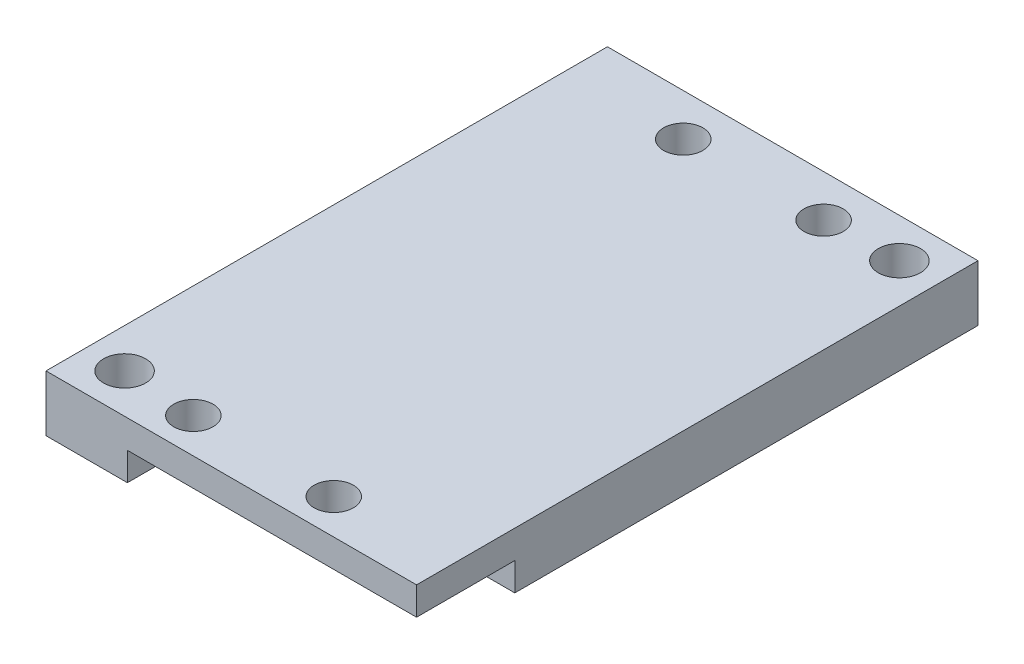
SolidWorks part; units mm, degrees
ref_plane "前视基准面" through (0, 0, 0) normal (0, 0, 1) x (1, 0, 0)
ref_plane "上视基准面" through (0, 0, 0) normal (0, 1, 0) x (1, 0, 0)
ref_plane "右视基准面" through (0, 0, 0) normal (1, 0, 0) x (0, 0, -1)
other "Configuration Table"
sketch "草图1" plane through (0, 0, 0) normal (0, 1, 0) x (1, 0, 0)
  line L1 (-6.6, 10) -> (6.6, 10)
  line L2 (-6.6, 10) -> (-6.6, -10)
  line L3 (-6.6, -10) -> (6.6, -10)
  line L4 (6.6, 10) -> (6.6, -10)
  line L5 (-6.6, 10) -> (6.6, -10) construction
  line L6 (-6.6, -10) -> (6.6, 10) construction
  circle A0 centre (-5.2, -8.6) radius 0.75
  circle A1 centre (5.2, 8.6) radius 0.75
  point P0 (0, 0)
  point P5 (3, -8.5)
  dimension "D7" = 1.5
  dimension "D1" = 20
  dimension "D2" = 13.2
  dimension "D3" = 1.4
  dimension "D4" = 1.4
  dimension "D5" = 1.4
  dimension "D6" = 1.4
extrude "凸台-拉伸1" add sketch "草图1" along normal blind 2 contours L2 L3 L4 L1
extrude "切除-拉伸2" cut sketch "草图1<3>" along normal through all contours A0 | A1
sketch "草图1<3>" plane through (0, 0, 0) normal (0, 1, 0) x (1, 0, 0) same geometry as "草图1"
sketch "草图2" plane through (0, 2, 0) normal (0, 1, 0) x (1, 0, 0)
  line L0 (6.6, 10) -> (6.6, -10) construction
  line L1 (-6.6, 10) -> (3.7, 10)
  line L2 (-6.6, 10) -> (-6.6, 6.5)
  line L3 (-6.6, 6.5) -> (3.7, 6.5)
  line L4 (3.7, 10) -> (3.7, 6.5)
  line L5 (6.6, -10) -> (-3.7, -10)
  line L6 (6.6, -10) -> (6.6, -6.5)
  line L7 (6.6, -6.5) -> (-3.7, -6.5)
  line L8 (-3.7, -10) -> (-3.7, -6.5)
  line L9 (-6.6, -10) -> (6.6, -10) construction
  line L10 (6.6, 10) -> (6.6, -10) construction
  line L11 (-6.6, 10) -> (-6.6, -10) construction
  circle A0 centre (-2.6, -8.75) radius 0.7
  circle A1 centre (2.4, -8.75) radius 0.7
  circle A2 centre (-2.4, 8.5) radius 0.7
  circle A3 centre (2.6, 8.5) radius 0.7
  dimension "D5" = 1.4
  dimension "D1" = 3.5
  dimension "D2" = 10.3
  dimension "D3" = 4
  dimension "D4" = 5
  dimension "D6" = 1.25
  dimension "D7" = 1.5
  dimension "D8" = 5
  dimension "D9" = 4
extrude "切除-拉伸1" cut sketch "草图2" along normal blind 1 from surface contours L1 L4 L3 L2 | L7 L8 L5 L6 starting at face at (-5.2, 0, 9.35)
extrude "切除-拉伸4" cut sketch "草图2<3>" against normal through all contours A0 | A1 | A2 | A3
sketch "草图2<3>" plane through (0, 2, 0) normal (0, 1, 0) x (1, 0, 0) same geometry as "草图2"
